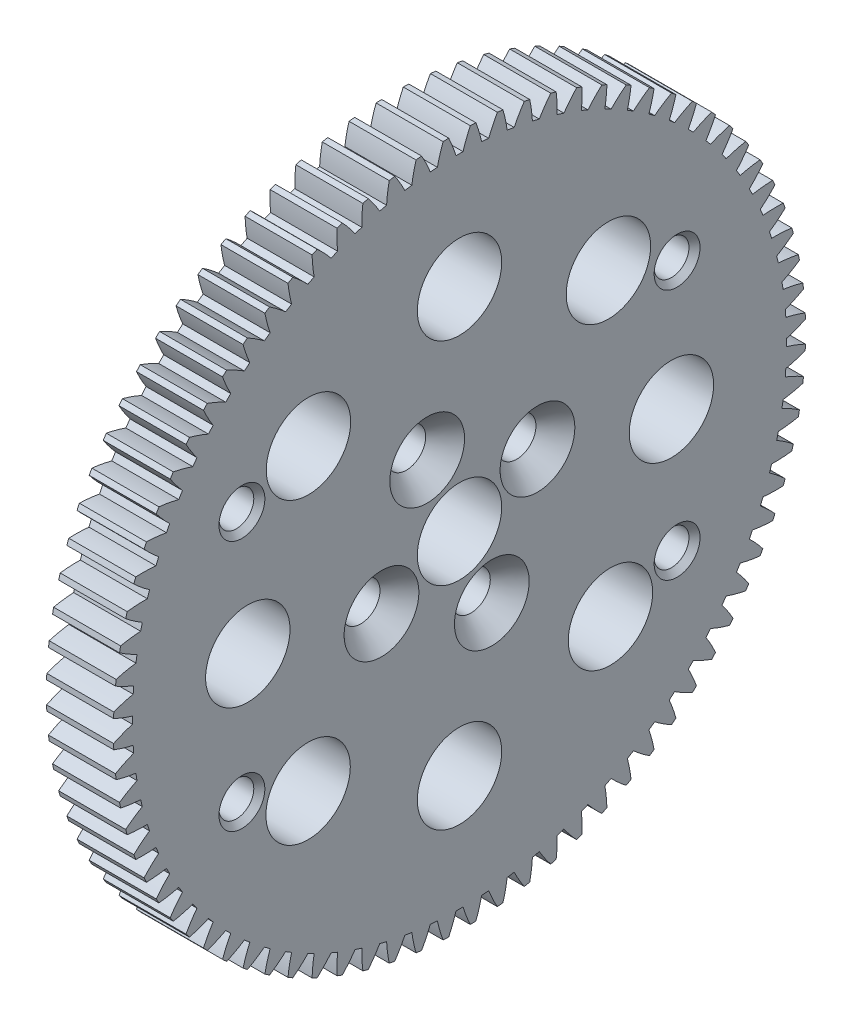
SolidWorks part; units mm, degrees
material "2024 Alloy"
ref_plane "Front Plane" through (0, 0, 0) normal (0, 0, 1) x (1, 0, 0)
ref_plane "Top Plane" through (0, 0, 0) normal (0, 1, 0) x (1, 0, 0)
ref_plane "Right Plane" through (0, 0, 0) normal (1, 0, 0) x (0, 0, -1)
ref_plane "Plane1" through (0, 0, 0) normal (-1, 0, 0) x (0, -1, 0)
ref_axis "Axis1" through (-3.4925, 0, 0) along (1, 0, 0)
sketch "Sketch1" plane through (0, 0, 0) normal (-1, 0, 0) x (0, -1, 0)
  line L0 (3.0615, 7.391) -> (-3.0615, -7.391) construction
  line L1 (7.391, -3.0615) -> (-7.391, 3.0615) construction
  circle A0 centre (0, 0) radius 4
  circle A1 centre (3.0615, 7.391) radius 1.75
  circle A2 centre (-20.084, 0) radius 4
  circle A3 centre (20.0633, 0) radius 4
  circle A4 centre (0, -20.084) radius 4
  circle A5 centre (0, 20.0633) radius 4
  circle A6 centre (-14.3663, -14.1126) radius 4
  circle A7 centre (14.142, -14.3069) radius 4
  circle A8 centre (14.1351, 14.3483) radius 4
  circle A9 centre (-14.1597, 14.315) radius 4
  circle A10 centre (-7.391, 3.0615) radius 1.75
  circle A11 centre (7.391, -3.0615) radius 1.75
  circle A12 centre (-3.0615, -7.391) radius 1.75
  arc A13 (-32.5405, -4.1179) -> (-30.6681, -4.5175) centre (-28.9403, 8.1654) ccw
  arc A14 (-30.6681, -4.5175) -> (-30.563, -5.1806) centre (0, 0) ccw
  arc A15 (-30.563, -5.1806) -> (-32.2203, -6.1392) centre (-25.0006, -16.7088) ccw
  arc A16 (-32.2203, -6.1392) -> (-32.1171, -6.6583) centre (0, 0) ccw
  arc A17 (-32.1171, -6.6583) -> (-30.2191, -6.9097) centre (-29.4917, 5.8696) ccw
  arc A18 (-30.2191, -6.9097) -> (-30.0624, -7.5626) centre (0, 0) ccw
  arc A19 (-30.0624, -7.5626) -> (-31.6393, -8.6483) centre (-23.6126, -18.6188) ccw
  arc A20 (-31.6393, -8.6483) -> (-31.4957, -9.1576) centre (0, 0) ccw
  arc A21 (-31.4957, -9.1576) -> (-29.5838, -9.2594) centre (-29.8613, 3.5376) ccw
  arc A22 (-29.5838, -9.2594) -> (-29.3763, -9.8979) centre (0, 0) ccw
  arc A23 (-29.3763, -9.8979) -> (-30.8633, -11.104) centre (-22.079, -20.414) ccw
  arc A24 (-30.8633, -11.104) -> (-30.6801, -11.6005) centre (0, 0) ccw
  arc A25 (-30.6801, -11.6005) -> (-28.7661, -11.552) centre (-30.0469, 1.1838) ccw
  arc A26 (-28.7661, -11.552) -> (-28.5092, -12.1723) centre (0, 0) ccw
  arc A27 (-28.5092, -12.1723) -> (-29.8969, -13.4913) centre (-20.4093, -22.0834) ccw
  arc A28 (-29.8969, -13.4913) -> (-29.6753, -13.9719) centre (0, 0) ccw
  arc A29 (-29.6753, -13.9719) -> (-27.7711, -13.7733) centre (-30.0471, -1.1773) ccw
  arc A30 (-27.7711, -13.7733) -> (-27.4663, -14.3715) centre (0, 0) ccw
  arc A31 (-27.4663, -14.3715) -> (-28.7462, -15.7954) centre (-18.6137, -23.6166) ccw
  arc A32 (-28.7462, -15.7954) -> (-28.4876, -16.2571) centre (0, 0) ccw
  arc A33 (-28.4876, -16.2571) -> (-26.6048, -15.9097) centre (-29.8621, -3.5311) ccw
  arc A34 (-26.6048, -15.9097) -> (-26.254, -16.4822) centre (0, 0) ccw
  arc A35 (-26.254, -16.4822) -> (-27.4183, -18.0021) centre (-16.7034, -25.0042) ccw
  arc A36 (-27.4183, -18.0021) -> (-27.1243, -18.4421) centre (0, 0) ccw
  arc A37 (-27.1243, -18.4421) -> (-25.2746, -17.9481) centre (-29.493, -5.8632) ccw
  arc A38 (-25.2746, -17.9481) -> (-24.8799, -18.4913) centre (0, 0) ccw
  arc A39 (-24.8799, -18.4913) -> (-25.9214, -20.0978) centre (-14.6901, -26.2377) ccw
  arc A40 (-25.9214, -20.0978) -> (-25.5937, -20.5134) centre (0, 0) ccw
  arc A41 (-25.5937, -20.5134) -> (-23.7885, -19.8758) centre (-28.9421, -8.1591) ccw
  arc A42 (-23.7885, -19.8758) -> (-23.3524, -20.3863) centre (0, 0) ccw
  arc A43 (-23.3524, -20.3863) -> (-24.2646, -22.0696) centre (-12.5862, -27.3094) ccw
  arc A44 (-24.2646, -22.0696) -> (-23.9054, -22.4582) centre (0, 0) ccw
  arc A45 (-23.9054, -22.4582) -> (-22.1557, -21.6809) centre (-28.2127, -10.4047) ccw
  arc A46 (-22.1557, -21.6809) -> (-21.6809, -22.1557) centre (0, 0) ccw
  arc A47 (-21.6809, -22.1557) -> (-22.4582, -23.9054) centre (-10.4047, -28.2127) ccw
  arc A48 (-22.4582, -23.9054) -> (-22.0696, -24.2646) centre (0, 0) ccw
  arc A49 (-22.0696, -24.2646) -> (-20.3863, -23.3524) centre (-27.3094, -12.5862) ccw
  arc A50 (-20.3863, -23.3524) -> (-19.8758, -23.7885) centre (0, 0) ccw
  arc A51 (-19.8758, -23.7885) -> (-20.5134, -25.5937) centre (-8.1591, -28.9421) ccw
  arc A52 (-20.5134, -25.5937) -> (-20.0978, -25.9214) centre (0, 0) ccw
  arc A53 (-20.0978, -25.9214) -> (-18.4913, -24.8799) centre (-26.2377, -14.6901) ccw
  arc A54 (-18.4913, -24.8799) -> (-17.9481, -25.2746) centre (0, 0) ccw
  arc A55 (-17.9481, -25.2746) -> (-18.4421, -27.1243) centre (-5.8632, -29.493) ccw
  arc A56 (-18.4421, -27.1243) -> (-18.0021, -27.4183) centre (0, 0) ccw
  arc A57 (-18.0021, -27.4183) -> (-16.4822, -26.254) centre (-25.0042, -16.7034) ccw
  arc A58 (-16.4822, -26.254) -> (-15.9097, -26.6048) centre (0, 0) ccw
  arc A59 (-15.9097, -26.6048) -> (-16.2571, -28.4876) centre (-3.5311, -29.8621) ccw
  arc A60 (-16.2571, -28.4876) -> (-15.7954, -28.7462) centre (0, 0) ccw
  arc A61 (-15.7954, -28.7462) -> (-14.3715, -27.4663) centre (-23.6166, -18.6137) ccw
  arc A62 (-14.3715, -27.4663) -> (-13.7733, -27.7711) centre (0, 0) ccw
  arc A63 (-13.7733, -27.7711) -> (-13.9719, -29.6753) centre (-1.1773, -30.0471) ccw
  arc A64 (-13.9719, -29.6753) -> (-13.4913, -29.8969) centre (0, 0) ccw
  arc A65 (-13.4913, -29.8969) -> (-12.1723, -28.5092) centre (-22.0834, -20.4093) ccw
  arc A66 (-12.1723, -28.5092) -> (-11.552, -28.7661) centre (0, 0) ccw
  arc A67 (-11.552, -28.7661) -> (-11.6005, -30.6801) centre (1.1838, -30.0469) ccw
  arc A68 (-11.6005, -30.6801) -> (-11.104, -30.8633) centre (0, 0) ccw
  arc A69 (-11.104, -30.8633) -> (-9.8979, -29.3763) centre (-20.414, -22.079) ccw
  arc A70 (-9.8979, -29.3763) -> (-9.2594, -29.5838) centre (0, 0) ccw
  arc A71 (-9.2594, -29.5838) -> (-9.1576, -31.4957) centre (3.5376, -29.8613) ccw
  arc A72 (-9.1576, -31.4957) -> (-8.6483, -31.6393) centre (0, 0) ccw
  arc A73 (-8.6483, -31.6393) -> (-7.5626, -30.0624) centre (-18.6188, -23.6126) ccw
  arc A74 (-7.5626, -30.0624) -> (-6.9097, -30.2191) centre (0, 0) ccw
  arc A75 (-6.9097, -30.2191) -> (-6.6583, -32.1171) centre (5.8696, -29.4917) ccw
  arc A76 (-6.6583, -32.1171) -> (-6.1392, -32.2203) centre (0, 0) ccw
  arc A77 (-6.1392, -32.2203) -> (-5.1806, -30.563) centre (-16.7088, -25.0006) ccw
  arc A78 (-5.1806, -30.563) -> (-4.5175, -30.6681) centre (0, 0) ccw
  arc A79 (-4.5175, -30.6681) -> (-4.1179, -32.5405) centre (8.1654, -28.9403) ccw
  arc A80 (-4.1179, -32.5405) -> (-3.5923, -32.6027) centre (0, 0) ccw
  arc A81 (-3.5923, -32.6027) -> (-2.7667, -30.8753) centre (-14.6958, -26.2345) ccw
  arc A82 (-2.7667, -30.8753) -> (-2.0973, -30.928) centre (0, 0) ccw
  arc A83 (-2.0973, -30.928) -> (-1.5521, -32.7633) centre (10.4109, -28.2104) ccw
  arc A84 (-1.5521, -32.7633) -> (-1.0233, -32.784) centre (0, 0) ccw
  arc A85 (-1.0233, -32.784) -> (-0.3357, -30.9972) centre (-12.5921, -27.3066) ccw
  arc A86 (-0.3357, -30.9972) -> (0.3357, -30.9972) centre (0, 0) ccw
  arc A87 (0.3357, -30.9972) -> (1.0233, -32.784) centre (12.5921, -27.3066) ccw
  arc A88 (1.0233, -32.784) -> (1.5521, -32.7633) centre (0, 0) ccw
  arc A89 (1.5521, -32.7633) -> (2.0973, -30.928) centre (-10.4109, -28.2104) ccw
  arc A90 (2.0973, -30.928) -> (2.7667, -30.8753) centre (0, 0) ccw
  arc A91 (2.7667, -30.8753) -> (3.5923, -32.6027) centre (14.6958, -26.2345) ccw
  arc A92 (3.5923, -32.6027) -> (4.1179, -32.5405) centre (0, 0) ccw
  arc A93 (4.1179, -32.5405) -> (4.5175, -30.6681) centre (-8.1654, -28.9403) ccw
  arc A94 (4.5175, -30.6681) -> (5.1806, -30.563) centre (0, 0) ccw
  arc A95 (5.1806, -30.563) -> (6.1392, -32.2203) centre (16.7088, -25.0006) ccw
  arc A96 (6.1392, -32.2203) -> (6.6583, -32.1171) centre (0, 0) ccw
  arc A97 (6.6583, -32.1171) -> (6.9097, -30.2191) centre (-5.8696, -29.4917) ccw
  arc A98 (6.9097, -30.2191) -> (7.5626, -30.0624) centre (0, 0) ccw
  arc A99 (7.5626, -30.0624) -> (8.6483, -31.6393) centre (18.6188, -23.6126) ccw
  arc A100 (8.6483, -31.6393) -> (9.1576, -31.4957) centre (0, 0) ccw
  arc A101 (9.1576, -31.4957) -> (9.2594, -29.5838) centre (-3.5376, -29.8613) ccw
  arc A102 (9.2594, -29.5838) -> (9.8979, -29.3763) centre (0, 0) ccw
  arc A103 (9.8979, -29.3763) -> (11.104, -30.8633) centre (20.414, -22.079) ccw
  arc A104 (11.104, -30.8633) -> (11.6005, -30.6801) centre (0, 0) ccw
  arc A105 (11.6005, -30.6801) -> (11.552, -28.7661) centre (-1.1838, -30.0469) ccw
  arc A106 (11.552, -28.7661) -> (12.1723, -28.5092) centre (0, 0) ccw
  arc A107 (12.1723, -28.5092) -> (13.4913, -29.8969) centre (22.0834, -20.4093) ccw
  arc A108 (13.4913, -29.8969) -> (13.9719, -29.6753) centre (0, 0) ccw
  arc A109 (13.9719, -29.6753) -> (13.7733, -27.7711) centre (1.1773, -30.0471) ccw
  arc A110 (13.7733, -27.7711) -> (14.3715, -27.4663) centre (0, 0) ccw
  arc A111 (14.3715, -27.4663) -> (15.7954, -28.7462) centre (23.6166, -18.6137) ccw
  arc A112 (15.7954, -28.7462) -> (16.2571, -28.4876) centre (0, 0) ccw
  arc A113 (16.2571, -28.4876) -> (15.9097, -26.6048) centre (3.5311, -29.8621) ccw
  arc A114 (15.9097, -26.6048) -> (16.4822, -26.254) centre (0, 0) ccw
  arc A115 (16.4822, -26.254) -> (18.0021, -27.4183) centre (25.0042, -16.7034) ccw
  arc A116 (18.0021, -27.4183) -> (18.4421, -27.1243) centre (0, 0) ccw
  arc A117 (18.4421, -27.1243) -> (17.9481, -25.2746) centre (5.8632, -29.493) ccw
  arc A118 (17.9481, -25.2746) -> (18.4913, -24.8799) centre (0, 0) ccw
  arc A119 (18.4913, -24.8799) -> (20.0978, -25.9214) centre (26.2377, -14.6901) ccw
  arc A120 (20.0978, -25.9214) -> (20.5134, -25.5937) centre (0, 0) ccw
  arc A121 (20.5134, -25.5937) -> (19.8758, -23.7885) centre (8.1591, -28.9421) ccw
  arc A122 (19.8758, -23.7885) -> (20.3863, -23.3524) centre (0, 0) ccw
  arc A123 (20.3863, -23.3524) -> (22.0696, -24.2646) centre (27.3094, -12.5862) ccw
  arc A124 (22.0696, -24.2646) -> (22.4582, -23.9054) centre (0, 0) ccw
  arc A125 (22.4582, -23.9054) -> (21.6809, -22.1557) centre (10.4047, -28.2127) ccw
  arc A126 (21.6809, -22.1557) -> (22.1557, -21.6809) centre (0, 0) ccw
  arc A127 (22.1557, -21.6809) -> (23.9054, -22.4582) centre (28.2127, -10.4047) ccw
  arc A128 (23.9054, -22.4582) -> (24.2646, -22.0696) centre (0, 0) ccw
  arc A129 (24.2646, -22.0696) -> (23.3524, -20.3863) centre (12.5862, -27.3094) ccw
  arc A130 (23.3524, -20.3863) -> (23.7885, -19.8758) centre (0, 0) ccw
  arc A131 (23.7885, -19.8758) -> (25.5937, -20.5134) centre (28.9421, -8.1591) ccw
  arc A132 (25.5937, -20.5134) -> (25.9214, -20.0978) centre (0, 0) ccw
  arc A133 (25.9214, -20.0978) -> (24.8799, -18.4913) centre (14.6901, -26.2377) ccw
  arc A134 (24.8799, -18.4913) -> (25.2746, -17.9481) centre (0, 0) ccw
  arc A135 (25.2746, -17.9481) -> (27.1243, -18.4421) centre (29.493, -5.8632) ccw
  arc A136 (27.1243, -18.4421) -> (27.4183, -18.0021) centre (0, 0) ccw
  arc A137 (27.4183, -18.0021) -> (26.254, -16.4822) centre (16.7034, -25.0042) ccw
  arc A138 (26.254, -16.4822) -> (26.6048, -15.9097) centre (0, 0) ccw
  arc A139 (26.6048, -15.9097) -> (28.4876, -16.2571) centre (29.8621, -3.5311) ccw
  arc A140 (28.4876, -16.2571) -> (28.7462, -15.7954) centre (0, 0) ccw
  arc A141 (28.7462, -15.7954) -> (27.4663, -14.3715) centre (18.6137, -23.6166) ccw
  arc A142 (27.4663, -14.3715) -> (27.7711, -13.7733) centre (0, 0) ccw
  arc A143 (27.7711, -13.7733) -> (29.6753, -13.9719) centre (30.0471, -1.1773) ccw
  arc A144 (29.6753, -13.9719) -> (29.8969, -13.4913) centre (0, 0) ccw
  arc A145 (29.8969, -13.4913) -> (28.5092, -12.1723) centre (20.4093, -22.0834) ccw
  arc A146 (28.5092, -12.1723) -> (28.7661, -11.552) centre (0, 0) ccw
  arc A147 (28.7661, -11.552) -> (30.6801, -11.6005) centre (30.0469, 1.1838) ccw
  arc A148 (30.6801, -11.6005) -> (30.8633, -11.104) centre (0, 0) ccw
  arc A149 (30.8633, -11.104) -> (29.3763, -9.8979) centre (22.079, -20.414) ccw
  arc A150 (29.3763, -9.8979) -> (29.5838, -9.2594) centre (0, 0) ccw
  arc A151 (29.5838, -9.2594) -> (31.4957, -9.1576) centre (29.8613, 3.5376) ccw
  arc A152 (31.4957, -9.1576) -> (31.6393, -8.6483) centre (0, 0) ccw
  arc A153 (31.6393, -8.6483) -> (30.0624, -7.5626) centre (23.6126, -18.6188) ccw
  arc A154 (30.0624, -7.5626) -> (30.2191, -6.9097) centre (0, 0) ccw
  arc A155 (30.2191, -6.9097) -> (32.1171, -6.6583) centre (29.4917, 5.8696) ccw
  arc A156 (32.1171, -6.6583) -> (32.2203, -6.1392) centre (0, 0) ccw
  arc A157 (32.2203, -6.1392) -> (30.563, -5.1806) centre (25.0006, -16.7088) ccw
  arc A158 (30.563, -5.1806) -> (30.6681, -4.5175) centre (0, 0) ccw
  arc A159 (30.6681, -4.5175) -> (32.5405, -4.1179) centre (28.9403, 8.1654) ccw
  arc A160 (32.5405, -4.1179) -> (32.6027, -3.5923) centre (0, 0) ccw
  arc A161 (32.6027, -3.5923) -> (30.8753, -2.7667) centre (26.2345, -14.6958) ccw
  arc A162 (30.8753, -2.7667) -> (30.928, -2.0973) centre (0, 0) ccw
  arc A163 (30.928, -2.0973) -> (32.7633, -1.5521) centre (28.2104, 10.4109) ccw
  arc A164 (32.7633, -1.5521) -> (32.784, -1.0233) centre (0, 0) ccw
  arc A165 (32.784, -1.0233) -> (30.9972, -0.3357) centre (27.3066, -12.5921) ccw
  arc A166 (30.9972, -0.3357) -> (30.9972, 0.3357) centre (0, 0) ccw
  arc A167 (30.9972, 0.3357) -> (32.784, 1.0233) centre (27.3066, 12.5921) ccw
  arc A168 (32.784, 1.0233) -> (32.7633, 1.5521) centre (0, 0) ccw
  arc A169 (32.7633, 1.5521) -> (30.928, 2.0973) centre (28.2104, -10.4109) ccw
  arc A170 (30.928, 2.0973) -> (30.8753, 2.7667) centre (0, 0) ccw
  arc A171 (30.8753, 2.7667) -> (32.6027, 3.5923) centre (26.2345, 14.6958) ccw
  arc A172 (32.6027, 3.5923) -> (32.5405, 4.1179) centre (0, 0) ccw
  arc A173 (32.5405, 4.1179) -> (30.6681, 4.5175) centre (28.9403, -8.1654) ccw
  arc A174 (30.6681, 4.5175) -> (30.563, 5.1806) centre (0, 0) ccw
  arc A175 (30.563, 5.1806) -> (32.2203, 6.1392) centre (25.0006, 16.7088) ccw
  arc A176 (32.2203, 6.1392) -> (32.1171, 6.6583) centre (0, 0) ccw
  arc A177 (32.1171, 6.6583) -> (30.2191, 6.9097) centre (29.4917, -5.8696) ccw
  arc A178 (30.2191, 6.9097) -> (30.0624, 7.5626) centre (0, 0) ccw
  arc A179 (30.0624, 7.5626) -> (31.6393, 8.6483) centre (23.6126, 18.6188) ccw
  arc A180 (31.6393, 8.6483) -> (31.4957, 9.1576) centre (0, 0) ccw
  arc A181 (31.4957, 9.1576) -> (29.5838, 9.2594) centre (29.8613, -3.5376) ccw
  arc A182 (29.5838, 9.2594) -> (29.3763, 9.8979) centre (0, 0) ccw
  arc A183 (29.3763, 9.8979) -> (30.8633, 11.104) centre (22.079, 20.414) ccw
  arc A184 (30.8633, 11.104) -> (30.6801, 11.6005) centre (0, 0) ccw
  arc A185 (30.6801, 11.6005) -> (28.7661, 11.552) centre (30.0469, -1.1838) ccw
  arc A186 (28.7661, 11.552) -> (28.5092, 12.1723) centre (0, 0) ccw
  arc A187 (28.5092, 12.1723) -> (29.8969, 13.4913) centre (20.4093, 22.0834) ccw
  arc A188 (29.8969, 13.4913) -> (29.6753, 13.9719) centre (0, 0) ccw
  arc A189 (29.6753, 13.9719) -> (27.7711, 13.7733) centre (30.0471, 1.1773) ccw
  arc A190 (27.7711, 13.7733) -> (27.4663, 14.3715) centre (0, 0) ccw
  arc A191 (27.4663, 14.3715) -> (28.7462, 15.7954) centre (18.6137, 23.6166) ccw
  arc A192 (28.7462, 15.7954) -> (28.4876, 16.2571) centre (0, 0) ccw
  arc A193 (28.4876, 16.2571) -> (26.6048, 15.9097) centre (29.8621, 3.5311) ccw
  arc A194 (26.6048, 15.9097) -> (26.254, 16.4822) centre (0, 0) ccw
  arc A195 (26.254, 16.4822) -> (27.4183, 18.0021) centre (16.7034, 25.0042) ccw
  arc A196 (27.4183, 18.0021) -> (27.1243, 18.4421) centre (0, 0) ccw
  arc A197 (27.1243, 18.4421) -> (25.2746, 17.9481) centre (29.493, 5.8632) ccw
  arc A198 (25.2746, 17.9481) -> (24.8799, 18.4913) centre (0, 0) ccw
  arc A199 (24.8799, 18.4913) -> (25.9214, 20.0978) centre (14.6901, 26.2377) ccw
  arc A200 (25.9214, 20.0978) -> (25.5937, 20.5134) centre (0, 0) ccw
  arc A201 (25.5937, 20.5134) -> (23.7885, 19.8758) centre (28.9421, 8.1591) ccw
  arc A202 (23.7885, 19.8758) -> (23.3524, 20.3863) centre (0, 0) ccw
  arc A203 (23.3524, 20.3863) -> (24.2646, 22.0696) centre (12.5862, 27.3094) ccw
  arc A204 (24.2646, 22.0696) -> (23.9054, 22.4582) centre (0, 0) ccw
  arc A205 (23.9054, 22.4582) -> (22.1557, 21.6809) centre (28.2127, 10.4047) ccw
  arc A206 (22.1557, 21.6809) -> (21.6809, 22.1557) centre (0, 0) ccw
  arc A207 (21.6809, 22.1557) -> (22.4582, 23.9054) centre (10.4047, 28.2127) ccw
  arc A208 (22.4582, 23.9054) -> (22.0696, 24.2646) centre (0, 0) ccw
  arc A209 (22.0696, 24.2646) -> (20.3863, 23.3524) centre (27.3094, 12.5862) ccw
  arc A210 (20.3863, 23.3524) -> (19.8758, 23.7885) centre (0, 0) ccw
  arc A211 (19.8758, 23.7885) -> (20.5134, 25.5937) centre (8.1591, 28.9421) ccw
  arc A212 (20.5134, 25.5937) -> (20.0978, 25.9214) centre (0, 0) ccw
  arc A213 (20.0978, 25.9214) -> (18.4913, 24.8799) centre (26.2377, 14.6901) ccw
  arc A214 (18.4913, 24.8799) -> (17.9481, 25.2746) centre (0, 0) ccw
  arc A215 (17.9481, 25.2746) -> (18.4421, 27.1243) centre (5.8632, 29.493) ccw
  arc A216 (18.4421, 27.1243) -> (18.0021, 27.4183) centre (0, 0) ccw
  arc A217 (18.0021, 27.4183) -> (16.4822, 26.254) centre (25.0042, 16.7034) ccw
  arc A218 (16.4822, 26.254) -> (15.9097, 26.6048) centre (0, 0) ccw
  arc A219 (15.9097, 26.6048) -> (16.2571, 28.4876) centre (3.5311, 29.8621) ccw
  arc A220 (16.2571, 28.4876) -> (15.7954, 28.7462) centre (0, 0) ccw
  arc A221 (15.7954, 28.7462) -> (14.3715, 27.4663) centre (23.6166, 18.6137) ccw
  arc A222 (14.3715, 27.4663) -> (13.7733, 27.7711) centre (0, 0) ccw
  arc A223 (13.7733, 27.7711) -> (13.9719, 29.6753) centre (1.1773, 30.0471) ccw
  arc A224 (13.9719, 29.6753) -> (13.4913, 29.8969) centre (0, 0) ccw
  arc A225 (13.4913, 29.8969) -> (12.1723, 28.5092) centre (22.0834, 20.4093) ccw
  arc A226 (12.1723, 28.5092) -> (11.552, 28.7661) centre (0, 0) ccw
  arc A227 (11.552, 28.7661) -> (11.6005, 30.6801) centre (-1.1838, 30.0469) ccw
  arc A228 (11.6005, 30.6801) -> (11.104, 30.8633) centre (0, 0) ccw
  arc A229 (11.104, 30.8633) -> (9.8979, 29.3763) centre (20.414, 22.079) ccw
  arc A230 (9.8979, 29.3763) -> (9.2594, 29.5838) centre (0, 0) ccw
  arc A231 (9.2594, 29.5838) -> (9.1576, 31.4957) centre (-3.5376, 29.8613) ccw
  arc A232 (9.1576, 31.4957) -> (8.6483, 31.6393) centre (0, 0) ccw
  arc A233 (8.6483, 31.6393) -> (7.5626, 30.0624) centre (18.6188, 23.6126) ccw
  arc A234 (7.5626, 30.0624) -> (6.9097, 30.2191) centre (0, 0) ccw
  arc A235 (6.9097, 30.2191) -> (6.6583, 32.1171) centre (-5.8696, 29.4917) ccw
  arc A236 (6.6583, 32.1171) -> (6.1392, 32.2203) centre (0, 0) ccw
  arc A237 (6.1392, 32.2203) -> (5.1806, 30.563) centre (16.7088, 25.0006) ccw
  arc A238 (5.1806, 30.563) -> (4.5175, 30.6681) centre (0, 0) ccw
  arc A239 (4.5175, 30.6681) -> (4.1179, 32.5405) centre (-8.1654, 28.9403) ccw
  arc A240 (4.1179, 32.5405) -> (3.5923, 32.6027) centre (0, 0) ccw
  arc A241 (3.5923, 32.6027) -> (2.7667, 30.8753) centre (14.6958, 26.2345) ccw
  arc A242 (2.7667, 30.8753) -> (2.0973, 30.928) centre (0, 0) ccw
  arc A243 (2.0973, 30.928) -> (1.5521, 32.7633) centre (-10.4109, 28.2104) ccw
  arc A244 (1.5521, 32.7633) -> (1.0233, 32.784) centre (0, 0) ccw
  arc A245 (1.0233, 32.784) -> (0.3357, 30.9972) centre (12.5921, 27.3066) ccw
  arc A246 (0.3357, 30.9972) -> (-0.3357, 30.9972) centre (0, 0) ccw
  arc A247 (-0.3357, 30.9972) -> (-1.0233, 32.784) centre (-12.5921, 27.3066) ccw
  arc A248 (-1.0233, 32.784) -> (-1.5521, 32.7633) centre (0, 0) ccw
  arc A249 (-1.5521, 32.7633) -> (-2.0973, 30.928) centre (10.4109, 28.2104) ccw
  arc A250 (-2.0973, 30.928) -> (-2.7667, 30.8753) centre (0, 0) ccw
  arc A251 (-2.7667, 30.8753) -> (-3.5923, 32.6027) centre (-14.6958, 26.2345) ccw
  arc A252 (-3.5923, 32.6027) -> (-4.1179, 32.5405) centre (0, 0) ccw
  arc A253 (-4.1179, 32.5405) -> (-4.5175, 30.6681) centre (8.1654, 28.9403) ccw
  arc A254 (-4.5175, 30.6681) -> (-5.1806, 30.563) centre (0, 0) ccw
  arc A255 (-5.1806, 30.563) -> (-6.1392, 32.2203) centre (-16.7088, 25.0006) ccw
  arc A256 (-6.1392, 32.2203) -> (-6.6583, 32.1171) centre (0, 0) ccw
  arc A257 (-6.6583, 32.1171) -> (-6.9097, 30.2191) centre (5.8696, 29.4917) ccw
  arc A258 (-6.9097, 30.2191) -> (-7.5626, 30.0624) centre (0, 0) ccw
  arc A259 (-7.5626, 30.0624) -> (-8.6483, 31.6393) centre (-18.6188, 23.6126) ccw
  arc A260 (-8.6483, 31.6393) -> (-9.1576, 31.4957) centre (0, 0) ccw
  arc A261 (-9.1576, 31.4957) -> (-9.2594, 29.5838) centre (3.5376, 29.8613) ccw
  arc A262 (-9.2594, 29.5838) -> (-9.8979, 29.3763) centre (0, 0) ccw
  arc A263 (-9.8979, 29.3763) -> (-11.104, 30.8633) centre (-20.414, 22.079) ccw
  arc A264 (-11.104, 30.8633) -> (-11.6005, 30.6801) centre (0, 0) ccw
  arc A265 (-11.6005, 30.6801) -> (-11.552, 28.7661) centre (1.1838, 30.0469) ccw
  arc A266 (-11.552, 28.7661) -> (-12.1723, 28.5092) centre (0, 0) ccw
  arc A267 (-12.1723, 28.5092) -> (-13.4913, 29.8969) centre (-22.0834, 20.4093) ccw
  arc A268 (-13.4913, 29.8969) -> (-13.9719, 29.6753) centre (0, 0) ccw
  arc A269 (-13.9719, 29.6753) -> (-13.7733, 27.7711) centre (-1.1773, 30.0471) ccw
  arc A270 (-13.7733, 27.7711) -> (-14.3715, 27.4663) centre (0, 0) ccw
  arc A271 (-14.3715, 27.4663) -> (-15.7954, 28.7462) centre (-23.6166, 18.6137) ccw
  arc A272 (-15.7954, 28.7462) -> (-16.2571, 28.4876) centre (0, 0) ccw
  arc A273 (-16.2571, 28.4876) -> (-15.9097, 26.6048) centre (-3.5311, 29.8621) ccw
  arc A274 (-15.9097, 26.6048) -> (-16.4822, 26.254) centre (0, 0) ccw
  arc A275 (-16.4822, 26.254) -> (-18.0021, 27.4183) centre (-25.0042, 16.7034) ccw
  arc A276 (-18.0021, 27.4183) -> (-18.4421, 27.1243) centre (0, 0) ccw
  arc A277 (-18.4421, 27.1243) -> (-17.9481, 25.2746) centre (-5.8632, 29.493) ccw
  arc A278 (-17.9481, 25.2746) -> (-18.4913, 24.8799) centre (0, 0) ccw
  arc A279 (-18.4913, 24.8799) -> (-20.0978, 25.9214) centre (-26.2377, 14.6901) ccw
  arc A280 (-20.0978, 25.9214) -> (-20.5134, 25.5937) centre (0, 0) ccw
  arc A281 (-20.5134, 25.5937) -> (-19.8758, 23.7885) centre (-8.1591, 28.9421) ccw
  arc A282 (-19.8758, 23.7885) -> (-20.3863, 23.3524) centre (0, 0) ccw
  arc A283 (-20.3863, 23.3524) -> (-22.0696, 24.2646) centre (-27.3094, 12.5862) ccw
  arc A284 (-22.0696, 24.2646) -> (-22.4582, 23.9054) centre (0, 0) ccw
  arc A285 (-22.4582, 23.9054) -> (-21.6809, 22.1557) centre (-10.4047, 28.2127) ccw
  arc A286 (-21.6809, 22.1557) -> (-22.1557, 21.6809) centre (0, 0) ccw
  arc A287 (-22.1557, 21.6809) -> (-23.9054, 22.4582) centre (-28.2127, 10.4047) ccw
  arc A288 (-23.9054, 22.4582) -> (-24.2646, 22.0696) centre (0, 0) ccw
  arc A289 (-24.2646, 22.0696) -> (-23.3524, 20.3863) centre (-12.5862, 27.3094) ccw
  arc A290 (-23.3524, 20.3863) -> (-23.7885, 19.8758) centre (0, 0) ccw
  arc A291 (-23.7885, 19.8758) -> (-25.5937, 20.5134) centre (-28.9421, 8.1591) ccw
  arc A292 (-25.5937, 20.5134) -> (-25.9214, 20.0978) centre (0, 0) ccw
  arc A293 (-25.9214, 20.0978) -> (-24.8799, 18.4913) centre (-14.6901, 26.2377) ccw
  arc A294 (-24.8799, 18.4913) -> (-25.2746, 17.9481) centre (0, 0) ccw
  arc A295 (-25.2746, 17.9481) -> (-27.1243, 18.4421) centre (-29.493, 5.8632) ccw
  arc A296 (-27.1243, 18.4421) -> (-27.4183, 18.0021) centre (0, 0) ccw
  arc A297 (-27.4183, 18.0021) -> (-26.254, 16.4822) centre (-16.7034, 25.0042) ccw
  arc A298 (-26.254, 16.4822) -> (-26.6048, 15.9097) centre (0, 0) ccw
  arc A299 (-26.6048, 15.9097) -> (-28.4876, 16.2571) centre (-29.8621, 3.5311) ccw
  arc A300 (-28.4876, 16.2571) -> (-28.7462, 15.7954) centre (0, 0) ccw
  arc A301 (-28.7462, 15.7954) -> (-27.4663, 14.3715) centre (-18.6137, 23.6166) ccw
  arc A302 (-27.4663, 14.3715) -> (-27.7711, 13.7733) centre (0, 0) ccw
  arc A303 (-27.7711, 13.7733) -> (-29.6753, 13.9719) centre (-30.0471, 1.1773) ccw
  arc A304 (-29.6753, 13.9719) -> (-29.8969, 13.4913) centre (0, 0) ccw
  arc A305 (-29.8969, 13.4913) -> (-28.5092, 12.1723) centre (-20.4093, 22.0834) ccw
  arc A306 (-28.5092, 12.1723) -> (-28.7661, 11.552) centre (0, 0) ccw
  arc A307 (-28.7661, 11.552) -> (-30.6801, 11.6005) centre (-30.0469, -1.1838) ccw
  arc A308 (-30.6801, 11.6005) -> (-30.8633, 11.104) centre (0, 0) ccw
  arc A309 (-30.8633, 11.104) -> (-29.3763, 9.8979) centre (-22.079, 20.414) ccw
  arc A310 (-29.3763, 9.8979) -> (-29.5838, 9.2594) centre (0, 0) ccw
  arc A311 (-29.5838, 9.2594) -> (-31.4957, 9.1576) centre (-29.8613, -3.5376) ccw
  arc A312 (-31.4957, 9.1576) -> (-31.6393, 8.6483) centre (0, 0) ccw
  arc A313 (-31.6393, 8.6483) -> (-30.0624, 7.5626) centre (-23.6126, 18.6188) ccw
  arc A314 (-30.0624, 7.5626) -> (-30.2191, 6.9097) centre (0, 0) ccw
  arc A315 (-30.2191, 6.9097) -> (-32.1171, 6.6583) centre (-29.4917, -5.8696) ccw
  arc A316 (-32.1171, 6.6583) -> (-32.2203, 6.1392) centre (0, 0) ccw
  arc A317 (-32.2203, 6.1392) -> (-30.563, 5.1806) centre (-25.0006, 16.7088) ccw
  arc A318 (-30.563, 5.1806) -> (-30.6681, 4.5175) centre (0, 0) ccw
  arc A319 (-30.6681, 4.5175) -> (-32.5405, 4.1179) centre (-28.9403, -8.1654) ccw
  arc A320 (-32.5405, 4.1179) -> (-32.6027, 3.5923) centre (0, 0) ccw
  arc A321 (-32.6027, 3.5923) -> (-30.8753, 2.7667) centre (-26.2345, 14.6958) ccw
  arc A322 (-30.8753, 2.7667) -> (-30.928, 2.0973) centre (0, 0) ccw
  arc A323 (-30.928, 2.0973) -> (-32.7633, 1.5521) centre (-28.2104, -10.4109) ccw
  arc A324 (-32.7633, 1.5521) -> (-32.784, 1.0233) centre (0, 0) ccw
  arc A325 (-32.784, 1.0233) -> (-30.9972, 0.3357) centre (-27.3066, 12.5921) ccw
  arc A326 (-30.9972, 0.3357) -> (-30.9972, -0.3357) centre (0, 0) ccw
  arc A327 (-30.9972, -0.3357) -> (-32.784, -1.0233) centre (-27.3066, -12.5921) ccw
  arc A328 (-32.784, -1.0233) -> (-32.7633, -1.5521) centre (0, 0) ccw
  arc A329 (-32.7633, -1.5521) -> (-30.928, -2.0973) centre (-28.2104, 10.4109) ccw
  arc A330 (-30.928, -2.0973) -> (-30.8753, -2.7667) centre (0, 0) ccw
  arc A331 (-30.8753, -2.7667) -> (-32.6027, -3.5923) centre (-26.2345, -14.6958) ccw
  arc A332 (-32.6027, -3.5923) -> (-32.5405, -4.1179) centre (0, 0) ccw
  dimension "D1" = 12.084
  dimension "D2" = 16
  dimension "D3" = 3.5
  dimension "D4" = 22.5
extrude "Boss-Extrude1" add sketch "Sketch1" against normal mid plane 6.35
sketch "Sketch2" plane through (0, 0, 0) normal (1, 0, 0) x (0, 0, -1)
  circle A0 centre (0, 0) radius 32 construction
  dimension "D1" = 64
sketch "Sketch3" plane through (0, 0, 0) normal (1, 0, 0) x (0, 0, -1)
  circle A6 centre (0, 23.8125) radius 1.9939
  circle A7 centre (-20.6222, 11.9063) radius 1.9939
  circle A8 centre (-20.6222, -11.9063) radius 1.9939
  circle A9 centre (0, -23.8125) radius 1.9939
  circle A10 centre (20.6222, -11.9063) radius 1.9939
  circle A11 centre (20.6222, 11.9063) radius 1.9939
hole_wizard "M4x0.7 Tapped Hole1" positions "Sketch4" profile "Sketch5" tap size "M4x0.7" standard "ANSI Metric" end condition through all
sketch "Sketch4" plane through (3.175, 0, 0) normal (1, 0, 0) x (0, 0, -1)
  point P0 (-20.6222, 11.9063)
  point P3 (-20.6222, -11.9063)
  point P6 (20.6222, 11.9063)
  point P9 (20.6222, -11.9063)
sketch "Sketch5" plane through (3.175, 11.9063, 20.6222) normal (0, 1, 0) x (0, 0, -1)
  line L0 (0, 0) -> (0, 6.35)
  line L1 (0, 6.35) -> (2.175, 6.35)
  line L2 (1.65, 5.825) -> (1.65, 0.525)
  line L3 (1.65, 0.525) -> (2.175, 0)
  line L5 (2.175, 0) -> (0, 0)
  line L6 (-1.65, 0.525) -> (-2.175, 0) construction
  line L7 (2.175, 6.35) -> (1.65, 5.825)
  line L8 (-2.175, 6.35) -> (-1.65, 5.825) construction
  line L11 (0, -6.35) -> (0, 107.95) construction
  dimension "Thread Major Dia." = 3.3
  dimension "Thru Tap Drill Depth" = 6.35
  dimension "Near C'Sink Dia." = 4.35
  dimension "Near C'Sink Angle" = 90
  dimension "Far C'Sink Dia." = 4.35
  dimension "Far C'Sink Angle" = 90
hole_wizard "CSK for #6 Flat Head Machine Screw1" positions "Sketch6" profile "Sketch7" countersink size "#6" standard "ANSI Inch" end condition through all
sketch "Sketch6" plane through (3.175, 0, 0) normal (1, 0, 0) x (0, 0, -1)
  point P0 (7.391, 3.0615)
  point P3 (3.0615, -7.391)
  point P6 (-7.391, -3.0615)
  point P9 (-3.0615, 7.391)
sketch "Sketch7" plane through (3.175, 3.0615, -7.391) normal (0, 1, 0) x (0, 0, -1)
  line L0 (0, 0) -> (0, 6.35)
  line L1 (0, 6.35) -> (1.8288, 6.35)
  line L2 (1.8288, 6.35) -> (1.8288, 1.9723)
  line L3 (1.8288, 1.9723) -> (3.5433, 0)
  line L5 (3.5433, 0) -> (0, 0)
  line L6 (-1.8288, 1.9723) -> (-3.5433, 0) construction
  line L11 (0, -6.35) -> (0, 107.95) construction
  dimension "Thru Hole Dia." = 3.6576
  dimension "Thru Hole Depth" = 6.35
  dimension "Near C'Sink Dia." = 7.0866
  dimension "Near C'Sink Angle" = 82
